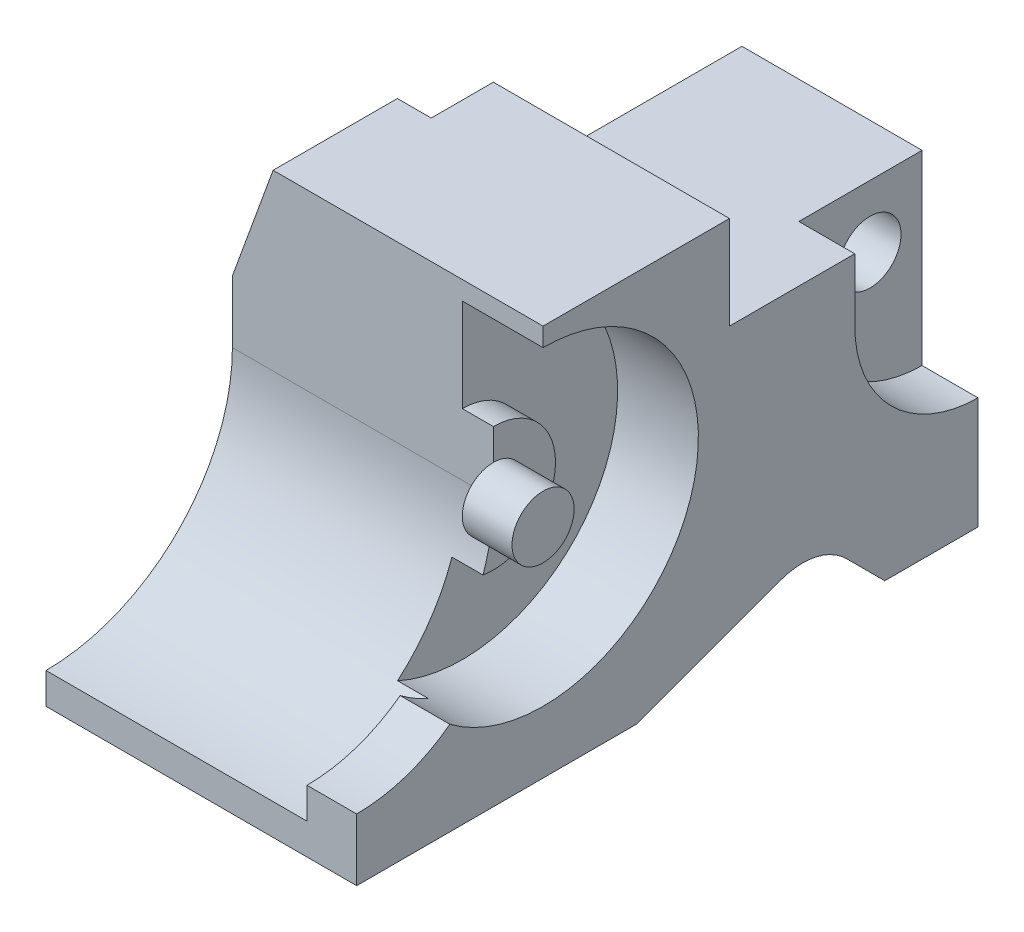
SolidWorks part; units mm, degrees
material "Copper"
ref_plane "Front Plane" through (0, 0, 0) normal (0, 0, 1) x (1, 0, 0)
ref_plane "Top Plane" through (0, 0, 0) normal (0, 1, 0) x (1, 0, 0)
ref_plane "Right Plane" through (0, 0, 0) normal (1, 0, 0) x (0, 0, -1)
sketch "Sketch1" plane through (0, 0, 0) normal (1, 0, 0) x (0, 0, -1)
  line L1 (-43.3502, 37.7485) -> (56.6498, 37.7485)
  line L2 (-43.3502, 37.7485) -> (-43.3502, -25.2515)
  line L3 (-43.3502, -25.2515) -> (56.6498, -25.2515)
  line L4 (56.6498, 37.7485) -> (56.6498, -25.2515)
  dimension "D1" = 100
  dimension "D2" = 63
extrude "Boss-Extrude1" add sketch "Sketch1" against normal blind 50
sketch "Sketch2" plane through (0, 37.7485, 0) normal (0, 1, 0) x (1, 0, 0)
  line L0 (0, 56.6498) -> (0, -43.3502) construction
  line L1 (-50, 56.6498) -> (0, 56.6498)
  line L2 (-50, 56.6498) -> (-50, 16.6498)
  line L3 (-50, 16.6498) -> (0, 16.6498)
  line L4 (0, 56.6498) -> (0, 16.6498)
  dimension "D1" = 40
extrude "Cut-Extrude1" cut sketch "Sketch2" against normal blind 15
sketch "Sketch3" plane through (0, 37.7485, 0) normal (0, 1, 0) x (1, 0, 0)
  line L1 (-50, 16.6498) -> (-38, 16.6498)
  line L2 (-50, 16.6498) -> (-50, 6.6498)
  line L3 (-50, 6.6498) -> (-38, 6.6498)
  line L4 (-38, 16.6498) -> (-38, 6.6498)
  dimension "D1" = 10
  dimension "D2" = 12
extrude "Cut-Extrude2" cut sketch "Sketch3" against normal blind 15
sketch "Sketch4" plane through (0, 0, 0) normal (1, 0, 0) x (0, 0, -1)
  line L0 (36.8141, 22.7485) -> (36.8141, 12.7485)
  line L1 (16.6498, 22.7485) -> (56.6498, 22.7485) construction
  line L2 (56.6498, -25.2515) -> (56.6498, 22.7485) construction
  line L3 (36.8141, 22.7485) -> (56.6498, 22.7485)
  line L4 (56.6498, 22.7485) -> (56.6498, -7.2508)
  arc A0 (36.8141, 12.7485) -> (56.6498, -7.2508) centre (56.8141, 12.7485) ccw
  dimension "D1" = 20
  dimension "D2" = 10
extrude "Cut-Extrude3" cut sketch "Sketch4" against normal blind 9
sketch "Sketch5" plane through (-9, 0, 0) normal (1, 0, 0) x (0, 0, -1)
  line L0 (56.6498, 22.7485) -> (36.8141, 22.7485) construction
  circle A0 centre (48.2591, 12.7485) radius 5
  dimension "D2" = 10
  dimension "D1" = 10
extrude "Cut-Extrude4" cut sketch "Sketch5" against normal through all
sketch "Sketch6" plane through (0, 0, 0) normal (1, 0, 0) x (0, 0, -1)
  line L0 (41.6498, -25.2515) -> (35.4807, -19.0824)
  line L1 (-43.3502, -25.2515) -> (56.6498, -25.2515) construction
  line L2 (24.9894, -16.7566) -> (1.6498, -25.2515)
  line L3 (56.6498, -25.2515) -> (56.6498, -7.2508) construction
  line L4 (1.6498, -25.2515) -> (41.6498, -25.2515)
  arc A0 (35.4807, -19.0824) -> (24.9894, -16.7566) centre (28.4096, -26.1535) ccw
  dimension "D3" = 10
  dimension "D1" = 15
  dimension "D2" = 45
  dimension "D4" = 20
  dimension "D5" = 40
extrude "Cut-Extrude5" cut sketch "Sketch6" against normal through all
sketch "Sketch8" plane through (-50, 0, 0) normal (-1, 0, 0) x (0, 0, 1)
  line L0 (64.957, 9.7485) -> (18.0256, 9.7485) construction
  line L1 (43.3502, -25.2515) -> (-1.6498, -25.2515) construction
  line L3 (43.3502, 9.7485) -> (43.3502, -20.2515)
  line L4 (13.3502, 37.7485) -> (43.3502, 37.7485)
  line L7 (13.3502, 9.7485) -> (13.3502, 37.7485)
  line L8 (43.3502, 9.7485) -> (13.3502, 9.7485)
  line L10 (13.3502, 37.7485) -> (36.7988, 37.7485)
  line L11 (-24.9894, -16.7566) -> (-1.6498, -25.2515)
  line L12 (-1.6498, -25.2515) -> (43.3502, -25.2515)
  line L16 (-6.6498, 22.7485) -> (-56.6498, 22.7485)
  line L17 (-56.6498, 22.7485) -> (-56.6498, -25.2515)
  line L18 (-56.6498, -25.2515) -> (-41.6498, -25.2515)
  line L19 (-41.6498, -25.2515) -> (-35.4807, -19.0824)
  line L20 (-24.9894, -16.7566) -> (-1.6498, -25.2515)
  line L25 (-6.6498, 22.7485) -> (-56.6498, 22.7485)
  line L26 (-56.6498, 22.7485) -> (-56.6498, -25.2515)
  line L27 (-56.6498, -25.2515) -> (-41.6498, -25.2515)
  line L28 (-41.6498, -25.2515) -> (-35.4807, -19.0824)
  line L36 (-1.6498, -25.2515) -> (43.3502, -25.2515)
  line L37 (43.3502, -25.2515) -> (43.3502, 37.7485)
  line L38 (43.3502, -25.2515) -> (43.3502, 37.7485)
  line L39 (43.3502, 37.7485) -> (-6.6498, 37.7485)
  line L40 (43.3502, 37.7485) -> (-6.6498, 37.7485)
  line L41 (-6.6498, 37.7485) -> (-6.6498, 22.7485)
  line L42 (-6.6498, 37.7485) -> (-6.6498, 22.7485)
  arc A0 (43.3502, -20.2515) -> (13.3502, 9.7485) centre (43.3502, 9.7485) cw
  arc A1 (-24.9894, -16.7566) -> (-35.4807, -19.0824) centre (-28.4096, -26.1535) ccw
  arc A2 (-24.9894, -16.7566) -> (-35.4807, -19.0824) centre (-28.4096, -26.1535) ccw
  point P4 (43.3502, 9.7485)
  line M19 (43.3502, -25.2515) -> (43.3502, 37.7485)
  line M20 (43.3502, 37.7485) -> (-6.6498, 37.7485)
  dimension "D3" = 30
  dimension "D1" = 35
  dimension "D2" = 0
extrude "Cut-Extrude6" cut sketch "Sketch8" against normal blind 42 contours A0 M19 region at (-50, -2.9839, 30.6178)
extrude "Cut-Extrude10" cut sketch "Sketch8<5>" against normal through all contours L8 L4 L7 M19 M20 region at (-50, 23.7485, 28.3502)
sketch "Sketch8<5>" plane through (-50, 0, 0) normal (-1, 0, 0) x (0, 0, 1) same geometry as "Sketch8"
sketch "Sketch11" plane through (0, 0, 0) normal (1, 0, 0) x (0, 0, -1)
  line L0 (-57.8609, 9.7485) -> (20.197, 9.7485) construction
  line L1 (-43.3502, -25.2515) -> (1.6498, -25.2515) construction
  line L2 (-13.3502, 44.713) -> (-13.3502, -34.9577) construction
  line L5 (-13.3502, 19.7485) -> (-13.3502, 14.7485)
  line L16 (-13.3502, 9.7485) -> (-43.3502, 9.7485)
  line L17 (-13.3502, 37.7485) -> (-13.3502, 9.7485)
  line L18 (-13.3502, 9.7485) -> (-43.3502, 9.7485)
  line L19 (-43.3502, 9.7485) -> (-43.3502, -25.2515)
  line L20 (-43.3502, -25.2515) -> (1.6498, -25.2515)
  line L21 (1.6498, -25.2515) -> (24.9894, -16.7566)
  line L22 (35.4807, -19.0824) -> (41.6498, -25.2515)
  line L23 (41.6498, -25.2515) -> (56.6498, -25.2515)
  line L24 (56.6498, -25.2515) -> (56.6498, -7.2508)
  line L25 (36.8141, 12.7485) -> (36.8141, 22.7485)
  line L26 (36.8141, 22.7485) -> (16.6498, 22.7485)
  line L27 (16.6498, 22.7485) -> (16.6498, 37.7485)
  line L28 (16.6498, 37.7485) -> (-13.3502, 37.7485)
  line L29 (-13.3502, 37.7485) -> (-13.3502, 9.7485)
  line L31 (-43.3502, 9.7485) -> (-43.3502, -25.2515)
  line L32 (-43.3502, -25.2515) -> (1.6498, -25.2515)
  line L33 (1.6498, -25.2515) -> (24.9894, -16.7566)
  line L34 (35.4807, -19.0824) -> (41.6498, -25.2515)
  line L35 (41.6498, -25.2515) -> (56.6498, -25.2515)
  line L36 (56.6498, -25.2515) -> (56.6498, -7.2508)
  line L37 (36.8141, 12.7485) -> (36.8141, 22.7485)
  line L38 (36.8141, 22.7485) -> (16.6498, 22.7485)
  line L39 (16.6498, 22.7485) -> (16.6498, 37.7485)
  line L40 (16.6498, 37.7485) -> (-13.3502, 37.7485)
  circle A0 centre (-13.3502, 9.7485) radius 25
  arc A1 (-28.3502, -10.2515) -> (-43.3502, -15.2515) centre (-43.3502, 9.7485) cw
  circle A2 centre (-13.3502, 9.7485) radius 10
  circle A3 centre (-13.3502, 9.7485) radius 5
  arc A4 (35.4807, -19.0824) -> (24.9894, -16.7566) centre (28.4096, -26.1535) ccw
  arc A5 (36.8141, 12.7485) -> (56.6498, -7.2508) centre (56.8141, 12.7485) ccw
  arc A6 (35.4807, -19.0824) -> (24.9894, -16.7566) centre (28.4096, -26.1535) ccw
  arc A7 (36.8141, 12.7485) -> (56.6498, -7.2508) centre (56.8141, 12.7485) ccw
  point P10 (0, 0)
  point P11 (0, 0)
  point P14 (0, 0)
  point P15 (0, 0)
  line M4 (-13.3502, 37.7485) -> (-13.3502, 9.7485)
  line M6 (-43.3502, 9.7485) -> (-43.3502, -25.2515)
  dimension "D3" = 50
  dimension "D4" = 25
  dimension "D6" = 10
  dimension "D7" = 20
  dimension "D1" = 35
  dimension "D2" = 30
  dimension "D5" = 0
extrude "Cut-Extrude16" cut sketch "Sketch11" against normal blind 13 contours A2 L18 A0 L29 region at (0, 27.2485, 12.6431)
extrude "Cut-Extrude17" cut sketch "Sketch11<8>" against normal blind 8 contours A3 A2 M4 region at (0, 16.6196, 6.4792)
sketch "Sketch11<8>" plane through (0, 0, 0) normal (1, 0, 0) x (0, 0, -1) same geometry as "Sketch11"
extrude "Boss-Extrude5" add sketch "Sketch11<10>" against normal blind 8 contours A3 M4 region at (0, 11.8706, 15.4723)
sketch "Sketch11<10>" plane through (0, 0, 0) normal (1, 0, 0) x (0, 0, -1) same geometry as "Sketch11"
sketch "Sketch14" plane through (0, 0, 13.3502) normal (0, 0, 1) x (1, 0, 0)
  line L0 (-50, 19.7485) -> (-43.4485, 37.7485)
  line L3 (-50, 9.7485) -> (-50, 37.7485) construction
  line L4 (0, 37.7485) -> (-50, 37.7485) construction
  line L5 (-50, 19.7485) -> (-50, 37.7485)
  line L6 (-50, 37.7485) -> (-43.4485, 37.7485)
  dimension "D1" = 20
  dimension "D2" = 18
extrude "Cut-Extrude18" cut sketch "Sketch14" against normal up to surface (20 mm away) up to face at (-44, 30.2485, -6.6498)
extrude "Cut-Extrude22" cut sketch "Sketch11<11>" against normal up to surface (8 mm away) contours A1 A0 L18 M6 region at (0, -4.6455, 38.5473) up to face at (-8, -4.4076, 37.8741)
sketch "Sketch11<11>" plane through (0, 0, 0) normal (1, 0, 0) x (0, 0, -1) same geometry as "Sketch11"
sketch "Sketch16" plane through (0, 22.7485, 0) normal (0, 1, 0) x (1, 0, 0)
  line L1 (-38, 6.6498) -> (-50, 6.6498)
  line L2 (-38, 6.6498) -> (-38, 56.6498)
  line L3 (-38, 56.6498) -> (-50, 56.6498)
  line L4 (-50, 6.6498) -> (-50, 56.6498)
extrude "Cut-Extrude23" cut sketch "Sketch16" against normal through all
